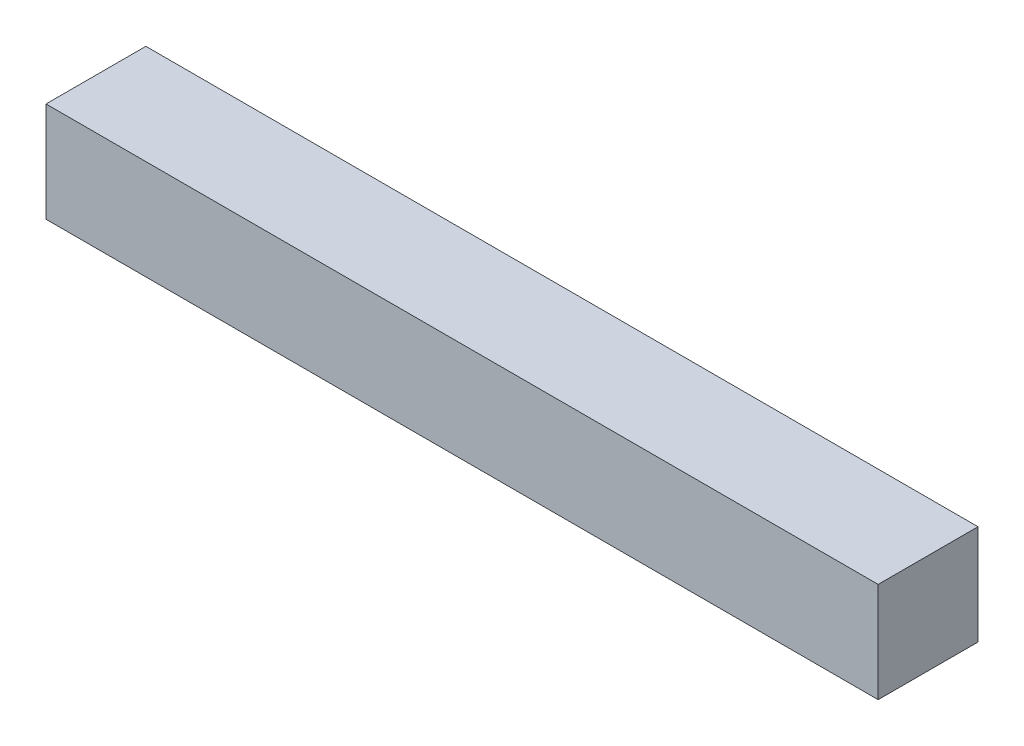
SolidWorks part; units mm, degrees
ref_plane "Płaszczyzna przednia" through (0, 0, 0) normal (0, 0, 1) x (1, 0, 0)
ref_plane "Płaszczyzna górna" through (0, 0, 0) normal (0, 1, 0) x (1, 0, 0)
ref_plane "Płaszczyzna prawa" through (0, 0, 0) normal (1, 0, 0) x (0, 0, -1)
sketch "Szkic1" plane through (0, 0, 0) normal (0, 0, 1) x (1, 0, 0)
  line L1 (-250, 30) -> (250, 30)
  line L2 (-250, 30) -> (-250, -30)
  line L3 (-250, -30) -> (250, -30)
  line L4 (250, 30) -> (250, -30)
  line L5 (-250, 30) -> (250, -30) construction
  line L6 (-250, -30) -> (250, 30) construction
  point P0 (0, 0)
  dimension "D1" = 500
  dimension "D2" = 60
extrude "Dodanie-wyciągnięcie1" add sketch "Szkic1" along normal blind 60
sketch "Szkic2" plane through (0, 0, 0) normal (0, 0, -1) x (-1, 0, 0)
  line L0 (0, 30) -> (0, -30) construction
  line L1 (-250, 30) -> (250, 30) construction
  line L2 (250, -30) -> (-250, -30) construction
  line L3 (-250, 0) -> (250, 0) construction
  line L4 (-250, -30) -> (-250, 30) construction
  line L5 (250, 30) -> (250, -30) construction
  line L6 (-250, 30) -> (0, 30) construction
  line L7 (0, 30) -> (250, 30) construction
  line L8 (-125, 30) -> (-125, -30) construction
  line L9 (125, 30) -> (125, -30) construction
  line L10 (-250, -30) -> (-125, -30) construction
  line L11 (-125, -30) -> (0, -30) construction
  line L12 (0, -30) -> (125, -30) construction
  line L13 (125, -30) -> (250, -30) construction
  line L14 (-187.5, -30) -> (-187.5, 30) construction
  line L15 (-62.5, -30) -> (-62.5, 30) construction
  line L16 (62.5, -30) -> (62.5, 30) construction
  line L17 (187.5, -30) -> (187.5, 30) construction
  circle A0 centre (-187.5, 0) radius 25
  circle A1 centre (-125, 0) radius 25
  circle A2 centre (-62.5, 0) radius 25
  circle A3 centre (0, 0) radius 25
  circle A4 centre (62.5, 0) radius 25
  circle A5 centre (125, 0) radius 25
  circle A6 centre (187.5, 0) radius 25
  dimension "D1" = 50
  dimension "D2" = 50
  dimension "D3" = 50
  dimension "D4" = 50
  dimension "D5" = 50
  dimension "D6" = 50
  dimension "D7" = 50
extrude "Wytnij-wyciągnięcie1" cut sketch "Szkic2" against normal blind 25
fillet "Zaokrąglenie2" radius 25 7 edges at (162.5, 0, 25) (-212.5, 0, 25) (-150, 0, 25) (-87.5, 0, 25) (-25, 0, 25) (37.5, 0, 25) (100, 0, 25)
